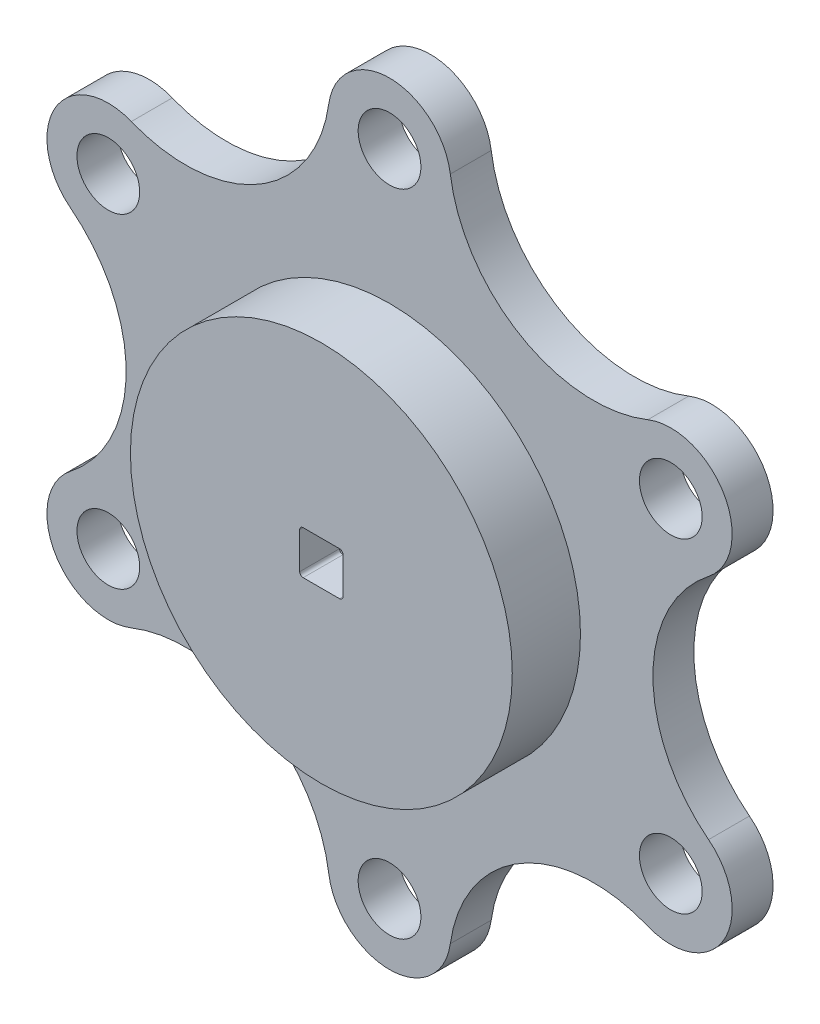
SolidWorks part; units mm, degrees
ref_plane "Front Plane" through (0, 0, 0) normal (0, 0, 1) x (1, 0, 0)
ref_plane "Top Plane" through (0, 0, 0) normal (0, 1, 0) x (1, 0, 0)
ref_plane "Right Plane" through (0, 0, 0) normal (1, 0, 0) x (0, 0, -1)
sketch "Sketch1" plane through (0, 0, 0) normal (0, 0, 1) x (1, 0, 0)
  circle A0 centre (0, 23.8125) radius 2.3
  circle A1 centre (0, 23.8125) radius 4.5
  circle A2 centre (20.6222, 11.9062) radius 4.5
  circle A3 centre (20.6222, 11.9062) radius 2.3
  circle A4 centre (20.6222, -11.9063) radius 4.5
  circle A5 centre (20.6222, -11.9063) radius 2.3
  circle A6 centre (0, -23.8125) radius 4.5
  circle A7 centre (0, -23.8125) radius 2.3
  circle A8 centre (-20.6222, -11.9062) radius 4.5
  circle A9 centre (-20.6222, -11.9062) radius 2.3
  circle A10 centre (-20.6222, 11.9063) radius 4.5
  circle A11 centre (-20.6222, 11.9063) radius 2.3
  circle A12 centre (0, 0) radius 19.3125
  circle A13 centre (-14.9587, 25.9093) radius 10.605
  circle A14 centre (14.9587, 25.9093) radius 10.605
  circle A15 centre (29.9175, 0) radius 10.605
  circle A16 centre (14.9587, -25.9093) radius 10.605
  circle A17 centre (-14.9587, -25.9093) radius 10.605
  circle A18 centre (-29.9175, 0) radius 10.605
  point P0 (0, 0)
  dimension "D2" = 4.6
  dimension "D3" = 9
  dimension "D1" = 23.8125
  dimension "D4" = 6
  dimension "D5" = 6
extrude "Boss-Extrude1" add sketch "Sketch1" along normal blind 3 contours A12 | A13 A10 A12 | A18 A12 A10 | A10 A11 | A13 A12 A1 | A1 A0 | A14 A1 A12 | A14 A12 A2 | A2 A3 | A15 A2 A12 | A15 A12 A4 | A4 A5 | A16 A4 A12 | A16 A12 A6 | A6 A7 | A17 A6 A12 | A17 A12 A8 | A8 A9 | A18 A8 A12 region at (3.092, 20.7205, 0) region at (4.7304, 19.9573, 0) region at (-4.7304, 19.9573, 0) region at (0, 0, 0) region at (14.9184, 14.0753, 0) region at (-14.9184, 14.0753, 0) region at (23.0668, 15.5318, 0) region at (19.6487, 5.882, 0) region at (-19.6487, 5.882, 0) region at (-19.7871, 7.614, 0) region at (19.6487, -5.882, 0) region at (-19.6487, -5.882, 0) region at (19.7871, -7.614, 0) region at (14.9184, -14.0753, 0) region at (-19.7871, -7.614, 0) region at (-14.9184, -14.0753, 0) region at (4.7304, -19.9573, 0) region at (-4.7304, -19.9573, 0) region at (3.092, -20.7205, 0)
sketch "Sketch2" plane through (0, 0, 3) normal (0, 0, 1) x (1, 0, 0)
  circle A0 centre (0, 0) radius 14
  dimension "D1" = 28
extrude "Boss-Extrude2" add sketch "Sketch2" along normal blind 5
sketch "Sketch3" plane through (0, 0, 0) normal (0, 0, -1) x (-1, 0, 0)
  line L1 (-1.5875, -1.5875) -> (1.5875, -1.5875)
  line L2 (-1.5875, -1.5875) -> (-1.5875, 1.5875)
  line L3 (-1.5875, 1.5875) -> (1.5875, 1.5875)
  line L4 (1.5875, -1.5875) -> (1.5875, 1.5875)
  line L5 (-1.5875, -1.5875) -> (1.5875, 1.5875) construction
  line L6 (-1.5875, 1.5875) -> (1.5875, -1.5875) construction
  line L7 (-3.175, -3.175) -> (3.175, -3.175)
  line L8 (-3.175, -3.175) -> (-3.175, 3.175)
  line L9 (-3.175, 3.175) -> (3.175, 3.175)
  line L10 (3.175, -3.175) -> (3.175, 3.175)
  line L11 (-3.175, -3.175) -> (3.175, 3.175) construction
  line L12 (-3.175, 3.175) -> (3.175, -3.175) construction
  circle A0 centre (0, 0) radius 5.08
  dimension "D2" = 10.16
  dimension "D1" = 3.175
  dimension "D3" = 6.35
extrude "Cut-Extrude1" cut sketch "Sketch3" against normal up to next contours L1 L4 L3 L2 region at (0, 0, 0)
extrude "Cut-Extrude2" cut sketch "Sketch3<3>" against normal blind 1.27 contours A0 L10 L7 L8 L9 | L7 L10 L9 L8 L4 L1 L2 L3 | L1 L4 L3 L2 region at (0, 0, 0) region at (3.0852, 0, 0) region at (4.9363, 0, 0)
sketch "Sketch3<3>" plane through (0, 0, 0) normal (0, 0, -1) x (-1, 0, 0) same geometry as "Sketch3"
extrude "Cut-Extrude3" cut sketch "Sketch3<4>" against normal blind 3.81 from surface contours L7 L10 L9 L8 L4 L1 L2 L3 region at (3.0852, 0, 0) starting at face at (-5.08, 0, 1.27)
sketch "Sketch3<4>" plane through (0, 0, 0) normal (0, 0, -1) x (-1, 0, 0) same geometry as "Sketch3"
fillet "Fillet1" radius 0.254 4 edges at (-1.5875, -1.5875, 6.54) (1.5875, -1.5875, 6.54) (1.5875, 1.5875, 6.54) (-1.5875, 1.5875, 6.54)
fillet "Fillet2" radius 0.635 4 edges at (3.175, -3.175, 3.175) (-3.175, -3.175, 3.175) (-3.175, 3.175, 3.175) (3.175, 3.175, 3.175)
